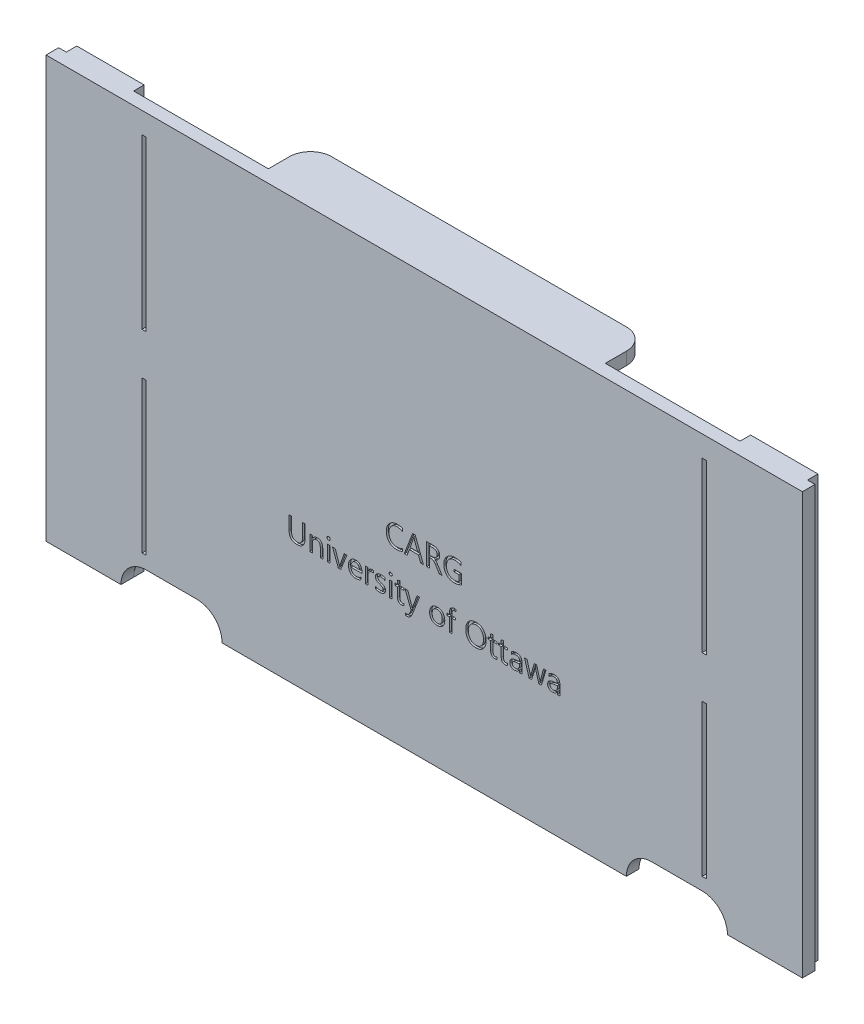
SolidWorks part; units mm, degrees
ref_plane "Front Plane" through (0, 0, 0) normal (0, 0, 1) x (1, 0, 0)
ref_plane "Top Plane" through (0, 0, 0) normal (0, 1, 0) x (1, 0, 0)
ref_plane "Right Plane" through (0, 0, 0) normal (1, 0, 0) x (0, 0, -1)
sketch "Sketch1" plane through (0, 0, 0) normal (0, 0, 1) x (1, 0, 0)
  line L1 (90, -50) -> (-90, -50)
  line L2 (90, -50) -> (90, 50)
  line L3 (90, 50) -> (-90, 50)
  line L4 (-90, -50) -> (-90, 50)
  line L5 (90, -50) -> (-90, 50) construction
  line L6 (90, 50) -> (-90, -50) construction
  point P0 (0, 0)
  dimension "D1" = 180
  dimension "D2" = 100
extrude "Boss-Extrude1" add sketch "Sketch1" along normal blind 3
sketch "Sketch2" plane through (0, 0, 0) normal (0, 0, -1) x (-1, 0, 0)
  line L0 (-80, 63.7201) -> (-80, -49936.2799) construction
  line L1 (80, 64.2305) -> (80, -49935.7695) construction
  dimension "D1" = 80
  dimension "D2" = 80
sketch "Sketch3" plane through (0, 0, 0) normal (0, 0, -1) x (-1, 0, 0)
  line L0 (-80, 200063.7201) -> (-80, -249936.2799) construction
  line L1 (-72, -50) -> (-88, -50)
  line L2 (-72, -50) -> (-72, 50)
  line L3 (-72, 50) -> (-88, 50)
  line L4 (-88, -50) -> (-88, 50)
  line L5 (-72, -50) -> (-88, 50) construction
  line L6 (-72, 50) -> (-88, -50) construction
  line L7 (-90, 50) -> (90, 50) construction
  line L8 (80, 200064.2305) -> (80, -249935.7695) construction
  line L9 (88, -50) -> (72, -50)
  line L10 (88, -50) -> (88, 50)
  line L11 (88, 50) -> (72, 50)
  line L12 (72, -50) -> (72, 50)
  line L13 (88, -50) -> (72, 50) construction
  line L14 (88, 50) -> (72, -50) construction
  point P0 (-80, 0)
  point P9 (80, 0)
  dimension "D1" = 16
  dimension "D2" = 16
extrude "Boss-Extrude2" add sketch "Sketch3" along normal blind 2.5
sketch "Sketch4" plane through (0, 0, -2.5) normal (0, 0, -1) x (-1, 0, 0)
  line L0 (-80, 200063.7201) -> (-80, -249936.2799) construction
  line L1 (-86.1, 47.75) -> (-73.9, 47.75)
  line L2 (-86.1, 47.75) -> (-86.1, 42.25)
  line L3 (-86.1, 42.25) -> (-73.9, 42.25)
  line L4 (-73.9, 47.75) -> (-73.9, 42.25)
  line L5 (-86.1, 47.75) -> (-73.9, 42.25) construction
  line L6 (-86.1, 42.25) -> (-73.9, 47.75) construction
  line L7 (-72, 50) -> (-88, 50) construction
  point P0 (-80, 45)
  dimension "D1" = 12.2
  dimension "D2" = 5
  dimension "D3" = 5.5
extrude "Cut-Extrude1" cut sketch "Sketch4" against normal blind 1.5
mirror "Mirror1" about plane through (0, 0, 0) normal (1, 0, 0) of "Cut-Extrude1"
pattern_linear "LPattern1" count 4 spacing 30 along (0, -1, 0) of "Mirror1"
sketch "Sketch5" plane through (0, 0, 3) normal (0, 0, 1) x (1, 0, 0)
  line L0 (-90, -10) -> (90, -10) construction
  line L1 (-90, 50) -> (-90, -50) construction
  line L2 (90, -50) -> (90, 50) construction
  text T0 "CARG\r\nUniversity of Ottawa" font "Yu Gothic UI" height in points 20
  dimension "D1" = 10
extrude "Cut-Extrude2" cut sketch "Sketch5" against normal blind 0.5
sketch "Sketch6" plane through (0, 50, 0) normal (0, 1, 0) x (1, 0, 0)
  line L0 (90, -3) -> (-90, -3) construction
  line L1 (-90, 0) -> (-89.8, 0)
  line L2 (-90, 0) -> (-90, -3)
  line L3 (-90, -3) -> (-89.8, -3)
  line L4 (-89.8, 0) -> (-89.8, -3)
  line L6 (90, 0) -> (89.8, 0)
  line L7 (90, 0) -> (90, -3)
  line L8 (90, -3) -> (89.8, -3)
  line L9 (89.8, 0) -> (89.8, -3)
  dimension "D1" = 0.2
  dimension "D2" = 0.2
extrude "Cut-Extrude3" cut sketch "Sketch6" against normal through all both and the other way through all
sketch "Sketch8" plane through (0, 0, 3) normal (0, 0, 1) x (1, 0, 0)
  line L0 (-60, 10.6106) -> (-60, -49989.3894) construction
  line L1 (60, 23.1735) -> (60, -49976.8265) construction
  dimension "D1" = 60
  dimension "D2" = 60
sketch "Sketch10" plane through (0, 0, 3) normal (0, 0, 1) x (1, 0, 0)
  line L0 (-66, -50) -> (-54, -50) construction
  line L1 (-60, 200010.6106) -> (-60, -249989.3894) construction
  line L2 (-89.8, -50) -> (89.8, -50) construction
  line L3 (-66, -44) -> (-54, -44)
  line L4 (-66, -56) -> (-54, -56)
  arc A0 (-66, -44) -> (-66, -56) centre (-66, -50) ccw
  arc A1 (-54, -56) -> (-54, -44) centre (-54, -50) ccw
  point P6 (-60, -50)
  dimension "D1" = 12
  dimension "D2" = 12
extrude "Cut-Extrude4" cut sketch "Sketch10" against normal through all both and the other way through all
mirror "Mirror3" about plane through (0, 0, 0) normal (1, 0, 0) of "Cut-Extrude4"
sketch "Sketch11" plane through (0, 0, -2.5) normal (0, 0, -1) x (-1, 0, 0)
  line L0 (-73.9, 12.25) -> (-80, -7.75)
  line L1 (-80, 200063.7201) -> (-80, -249936.2799) construction
  line L2 (-80, -7.75) -> (-86.1, 12.25)
  line L3 (-86.1, 12.25) -> (-73.9, 12.25)
  dimension "D1" = 20
extrude "Cut-Extrude5" cut sketch "Sketch11" against normal blind 1.5
pattern_linear "LPattern2" count 2 spacing 30 along (0, 1, 0) count 2 spacing 30 along (0, -1, 0) of "Cut-Extrude5" pattern seed only yes
mirror "Mirror4" about plane through (0, 0, 0) normal (1, 0, 0) of "LPattern2"
sketch "Sketch12" plane through (0, 0, -2.5) normal (0, 0, -1) x (-1, 0, 0)
  line L0 (-88, -50) -> (-72, -50) construction
  line L1 (-86.1, -47.75) -> (-73.9, -47.75)
  line L2 (-86.1, -47.75) -> (-86.1, -50)
  line L3 (-86.1, -50) -> (-73.9, -50)
  line L4 (-73.9, -47.75) -> (-73.9, -50)
extrude "Cut-Extrude6" cut sketch "Sketch12" against normal blind 1.5
mirror "Mirror5" about plane through (0, 0, 0) normal (1, 0, 0) of "Cut-Extrude6"
sketch "Sketch13" plane through (0, 0, 0) normal (0, 0, -1) x (-1, 0, 0)
  line L0 (-72, -50) -> (-72, 50) construction
  line L1 (-67, 45) -> (-66, 45)
  line L2 (-67, 45) -> (-67, 5)
  line L3 (-67, 5) -> (-66, 5)
  line L4 (-66, 45) -> (-66, 5)
  line L5 (-72, -50) -> (-72, 50) construction
  line L8 (-67, -5) -> (-66, -5)
  line L9 (-67, -5) -> (-67, -41)
  line L10 (-67, -41) -> (-66, -41)
  line L11 (-66, -5) -> (-66, -41)
  dimension "D1" = 5
  dimension "D2" = 1
  dimension "D3" = 40
  dimension "D4" = 5
  dimension "D5" = 5
  dimension "D6" = 36
  dimension "D7" = 5
  dimension "D8" = 1
extrude "Cut-Extrude7" cut sketch "Sketch13" against normal blind 10
mirror "Mirror7" about plane through (0, 0, 0) normal (1, 0, 0) of "Cut-Extrude7"
sketch "Sketch15" plane through (0, 0, 0) normal (0, 0, -1) x (-1, 0, 0)
  line L0 (-72, 50) -> (72, 50) construction
  line L1 (-40, 50) -> (40, 50)
  line L2 (-40, 50) -> (-40, 47)
  line L3 (-40, 47) -> (40, 47)
  line L4 (40, 50) -> (40, 47)
  dimension "D1" = 80
  dimension "D2" = 40
  dimension "D3" = 3
extrude "Boss-Extrude4" add sketch "Sketch15" along normal blind 10
fillet "Fillet2" radius 5 2 edges at (-40, 48.5, -10) (40, 48.5, -10)
fillet "Fillet3" radius 3 1 edges at (0, 47, 0)
